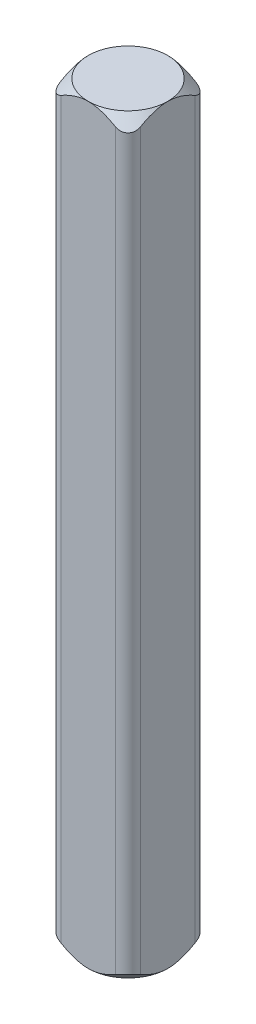
SolidWorks part; units mm, degrees
material "Plain Carbon Steel"
ref_plane "Front Plane" through (0, 0, 0) normal (0, 0, 1) x (1, 0, 0)
ref_plane "Top Plane" through (0, 0, 0) normal (0, 1, 0) x (1, 0, 0)
ref_plane "Right Plane" through (0, 0, 0) normal (1, 0, 0) x (0, 0, -1)
sketch "Sketch1" plane through (0, 0, 0) normal (0, 1, 0) x (1, 0, 0)
  line L1 (-1.5875, -1.5875) -> (1.5875, -1.5875)
  line L2 (-1.5875, -1.5875) -> (-1.5875, 1.5875)
  line L3 (-1.5875, 1.5875) -> (1.5875, 1.5875)
  line L4 (1.5875, -1.5875) -> (1.5875, 1.5875)
  line L5 (-1.5875, -1.5875) -> (1.5875, 1.5875) construction
  line L6 (-1.5875, 1.5875) -> (1.5875, -1.5875) construction
  point P0 (0, 0)
  dimension "D1" = 3.175
extrude "Boss-Extrude1" add sketch "Sketch1" along normal mid plane 30
ref_axis "a" through (0, 12.013, 0) along (0, -1, 0)
fillet "Fillet1" radius 0.508 4 edges at (-1.5875, 0, -1.5875) (-1.5875, 0, 1.5875) (1.5875, 0, -1.5875) (1.5875, 0, 1.5875)
sketch "Sketch3" plane through (0, 0, 0) normal (0, 0, 1) x (1, 0, 0)
  line L6 (0, 0) -> (0, -16.5875) construction
  line L7 (0, -16.5875) -> (1.5875, -15) construction
  line L8 (1.5875, -15) -> (2.2946, -14.2929)
  line L10 (-1.0795, -15) -> (1.0795, -15) construction
  line L11 (2.2946, -14.2929) -> (2.2946, -16)
  line L12 (2.2946, -16) -> (1.5875, -16)
  line L13 (1.5875, -15) -> (1.5875, -16)
  dimension "D1" = 45
  dimension "D2" = 1
  dimension "D3" = 1
revolve "Cut-Revolve3" cut sketch "Sketch3" angle 360 about L6
mirror "Mirror1" about plane through (0, 0, 0) normal (0, 1, 0) of "Cut-Revolve3"
equation "\"Length\"= \"Length@Boss-Extrude1\""
equation "\"Price\"= \"Length\" * 160 / ( 1m )"
